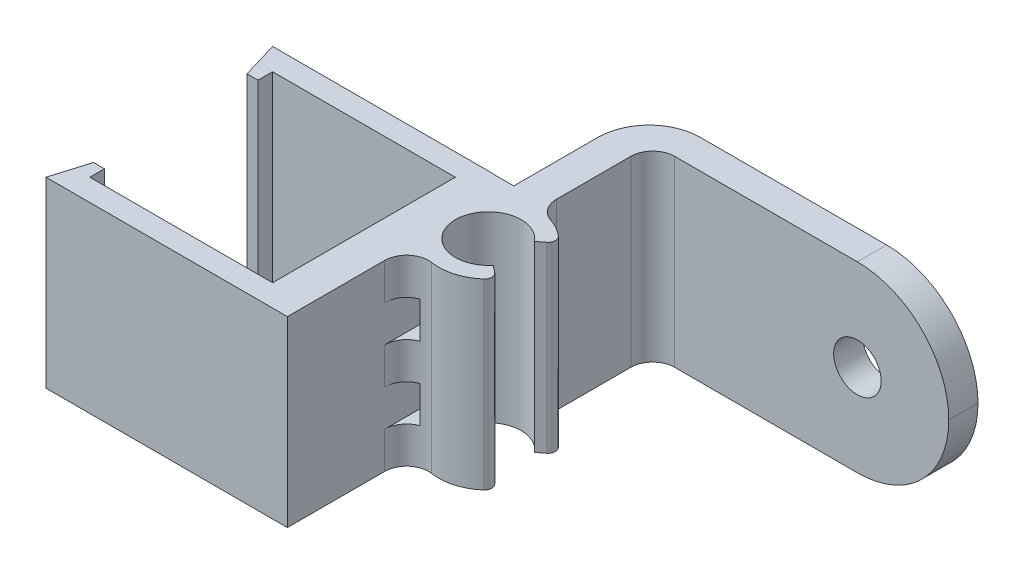
SolidWorks part; units mm, degrees
ref_plane "Спереди" through (0, 0, 0) normal (0, 0, 1) x (1, 0, 0)
ref_plane "Сверху" through (0, 0, 0) normal (0, 1, 0) x (1, 0, 0)
ref_plane "Справа" through (0, 0, 0) normal (1, 0, 0) x (0, 0, -1)
sketch "Эскиз1" plane through (0, 0, 0) normal (0, 1, 0) x (1, 0, 0)
  line L0 (-66.8258, 34.9697) -> (-66.8258, 29.9697)
  line L1 (-63.8258, 29.9697) -> (-63.8258, 31.9697)
  line L2 (-63.8258, 31.9697) -> (-38.8258, 31.9697)
  line L3 (-38.8258, 31.9697) -> (-38.8258, 6.9697)
  line L4 (-38.8258, 6.9697) -> (-63.8258, 6.9697)
  line L5 (-63.8258, 6.9697) -> (-63.8258, 8.9697)
  line L6 (-63.8258, 8.9697) -> (-66.8258, 8.9697)
  line L7 (-66.8258, 8.9697) -> (-66.8258, 3.9697)
  line L8 (-66.8258, 3.9697) -> (-22.1235, 3.9697)
  line L9 (-22.1235, 3.9697) -> (-36.579, 34.9697)
  line L10 (-36.579, 34.9697) -> (-66.8258, 34.9697)
  line L11 (-66.8258, 29.9697) -> (-63.8258, 29.9697)
  dimension "D1" = 25
  dimension "D2" = 25
  dimension "D3" = 25
  dimension "D4" = 155
  dimension "D5" = 3
  dimension "D6" = 3
  dimension "D7" = 3
  dimension "D8" = 3
  dimension "D9" = 2
  dimension "D10" = 2
extrude "Бобышка-Вытянуть1" add sketch "Эскиз1" along normal blind 25
sketch "Эскиз3" plane through (0, 0, 0) normal (0, -1, 0) x (1, 0, 0)
  line L0 (-66.8258, -3.9697) -> (-65.3258, -8.9697)
  line L1 (-63.8258, -8.9697) -> (-66.8258, -8.9697) construction
  line L2 (-65.3258, -8.9697) -> (-66.8258, -8.9697)
  line L3 (-66.8258, -8.9697) -> (-66.8258, -3.9697)
  line L4 (-66.8258, -29.9697) -> (-66.8258, -34.9697)
  line L5 (-66.8258, -34.9697) -> (-65.3258, -29.9697)
  line L6 (-66.8258, -29.9697) -> (-63.8258, -29.9697) construction
  line L7 (-65.3258, -29.9697) -> (-66.8258, -29.9697)
extrude "Вырез-Вытянуть4" cut sketch "Эскиз3" against normal through all
sketch "Эскиз7" plane through (0, 0, 0) normal (0, -1, 0) x (-1, 0, 0)
  line L1 (36.0076, 1.3029) -> (19.3993, 1.3029)
  line L2 (36.0076, 1.3029) -> (36.0076, 39.7765)
  line L3 (36.0076, 39.7765) -> (19.3993, 39.7765)
  line L4 (19.3993, 1.3029) -> (19.3993, 39.7765)
extrude "Вырез-Вытянуть14" cut sketch "Эскиз7" against normal through all
sketch "Эскиз8" plane through (0, 0, 0) normal (0, -1, 0) x (-1, 0, 0)
  line L0 (66.8258, 3.9697) -> (36.0076, 3.9697) construction
  line L1 (38.7989, 3.9697) -> (33.7989, 3.9697)
  line L2 (38.7989, 3.9697) -> (38.7989, 34.9383)
  line L3 (38.7989, 34.9383) -> (33.7989, 34.9383)
  line L4 (33.7989, 3.9697) -> (33.7989, 34.9383)
  dimension "D1" = 5
extrude "Бобышка-Вытянуть2" add sketch "Эскиз8" against normal up to surface (25 mm away) up to face at (-54.2963, 25, -20.5678)
sketch "Эскиз9" plane through (0, 0, 0) normal (0, -1, 0) x (1, 0, 0)
  line L0 (-33.7989, -19.454) -> (1.2661, -19.454) construction
  line L1 (-33.7989, -34.9383) -> (-33.7989, -3.9697) construction
  line L2 (-33.7989, -11.954) -> (-5.8657, -11.954) construction
  line L3 (-33.7989, -26.954) -> (-9.7824, -26.954) construction
  line L4 (-29.2989, -3.3613) -> (-29.2989, -35.1038) construction
  line L5 (-25.7989, -3.3613) -> (-25.7989, -35.1038) construction
  line L6 (-24.0009, -3.3613) -> (-24.0009, -34.4935) construction
  line L7 (-25.7989, -9.1217) -> (-24.0009, -7.6955)
  line L8 (-25.7989, -14.7863) -> (-24.0009, -16.2125)
  line L9 (-25.7989, -24.1307) -> (-24.0009, -22.7126)
  line L10 (-25.7989, -29.7773) -> (-24.0009, -31.1954)
  arc A0 (-25.7989, -9.1217) -> (-25.7989, -14.7863) centre (-29.2989, -11.954) ccw
  arc A1 (-25.7989, -24.1307) -> (-25.7989, -29.7773) centre (-29.2989, -26.954) ccw
  arc A2 (-24.0009, -7.6955) -> (-24.0009, -16.2125) centre (-29.2989, -11.954) ccw
  arc A3 (-24.0009, -22.7126) -> (-24.0009, -31.1954) centre (-29.2989, -26.954) ccw
  dimension "D1" = 7.5
  dimension "D2" = 7.5
  dimension "D3" = 4.5
  dimension "D4" = 3.5
extrude "Бобышка-Вытянуть3" add sketch "Эскиз9" against normal up to surface (25 mm away) up to face at (-52.7142, 25, -21.6795)
fillet "Скругление4" radius 1 4 edges at (-24.0009, 12.5, -7.6955) (-24.0009, 12.5, -16.2125) (-24.0009, 12.5, -31.1954) (-24.0009, 12.5, -22.7126)
sketch "Эскиз10" plane through (0, 25, 0) normal (0, 1, 0) x (1, 0, 0)
  line L1 (-33.7989, 3.9697) -> (-22.913, 3.9697)
  line L2 (-33.7989, 3.9697) -> (-33.7989, 20.0647)
  line L3 (-33.7989, 20.0647) -> (-22.913, 20.0647)
  line L4 (-22.913, 3.9697) -> (-22.913, 20.0647)
extrude "Вырез-Вытянуть15" cut sketch "Эскиз10" against normal through all
sketch "Эскиз11" plane through (0, 25, 0) normal (0, 1, 0) x (1, 0, 0)
  line L1 (-29.2989, 31.4508) -> (-33.7989, 31.4508)
  line L2 (-29.2989, 31.4508) -> (-29.2989, 53.4508)
  line L3 (-29.2989, 53.4508) -> (-33.7989, 53.4508)
  line L4 (-33.7989, 31.4508) -> (-33.7989, 53.4508)
  arc A0 (-25.7989, 29.7773) -> (-25.7989, 24.1307) centre (-29.2989, 26.954) ccw construction
  dimension "D1" = 22
  dimension "D2" = 4.5
extrude "Бобышка-Вытянуть5" add sketch "Эскиз11" against normal up to surface (25 mm away) up to face at (-43.811, 0, -23.5975)
sketch "Эскиз14" plane through (0, 25, 0) normal (0, 1, 0) x (1, 0, 0)
  line L0 (-33.7989, 53.4508) -> (-33.7989, 34.9383) construction
  line L1 (-33.7989, 53.4508) -> (11.2011, 53.4508)
  line L2 (-33.7989, 53.4508) -> (-33.7989, 49.4508)
  line L3 (-33.7989, 49.4508) -> (11.2011, 49.4508)
  line L4 (11.2011, 53.4508) -> (11.2011, 49.4508)
  dimension "D1" = 45
  dimension "D2" = 4
extrude "Бобышка-Вытянуть6" add sketch "Эскиз14" against normal up to surface (25 mm away) up to face at (-42.5951, 0, -26.1027)
sketch "Эскиз15" plane through (0, 0, -53.4508) normal (0, 0, -1) x (-1, 0, 0)
  line L0 (-11.2011, 12.5) -> (33.7989, 12.5) construction
  line L1 (-11.2011, 0) -> (-11.2011, 25) construction
  line L2 (33.7989, 25) -> (33.7989, 0) construction
  line L3 (1.2989, 25) -> (1.2989, 0) construction
  line L4 (-11.2011, 25) -> (33.7989, 25) construction
  line L5 (33.7989, 0) -> (-11.2011, 0) construction
  circle A0 centre (1.2989, 12.5) radius 3.25
  dimension "D1" = 12.5
extrude "Вырез-Вытянуть19" cut sketch "Эскиз15" against normal blind 10
fillet "Скругление5" radius 12.5 2 edges at (11.2011, 0, -51.4508) (11.2011, 25, -51.4508)
fillet "Скругление6" radius 3 1 edges at (-29.2989, 12.5, -49.4508)
fillet "Скругление7" radius 7 1 edges at (-33.7989, 12.5, -53.4508) tangent propagation no
fillet "Скругление8" radius 3 2 edges at (-29.2989, 12.5, -33.7407) (-33.7989, 12.5, -21.8737)
sketch "Эскиз17" plane through (0, 0, -3.9697) normal (0, 0, 1) x (1, 0, 0)
  line L0 (-33.7989, 25) -> (-33.7989, 0) construction
  line L1 (-33.7989, 20) -> (-31.7989, 20)
  line L2 (-33.7989, 20) -> (-33.7989, 15)
  line L3 (-33.7989, 15) -> (-31.7989, 15)
  line L4 (-31.7989, 20) -> (-31.7989, 15)
  line L5 (-30.3391, 25) -> (-33.7989, 25) construction
  line L6 (-33.7989, 0) -> (-30.3391, 0) construction
  line L7 (-33.7989, 10) -> (-31.7989, 10)
  line L8 (-33.7989, 10) -> (-33.7989, 5)
  line L9 (-33.7989, 5) -> (-31.7989, 5)
  line L10 (-31.7989, 10) -> (-31.7989, 5)
  dimension "D1" = 2
  dimension "D2" = 5
  dimension "D3" = 5
  dimension "D4" = 2
  dimension "D5" = 5
  dimension "D6" = 5
extrude "Вырез-Вытянуть21" cut sketch "Эскиз17" against normal blind 23
